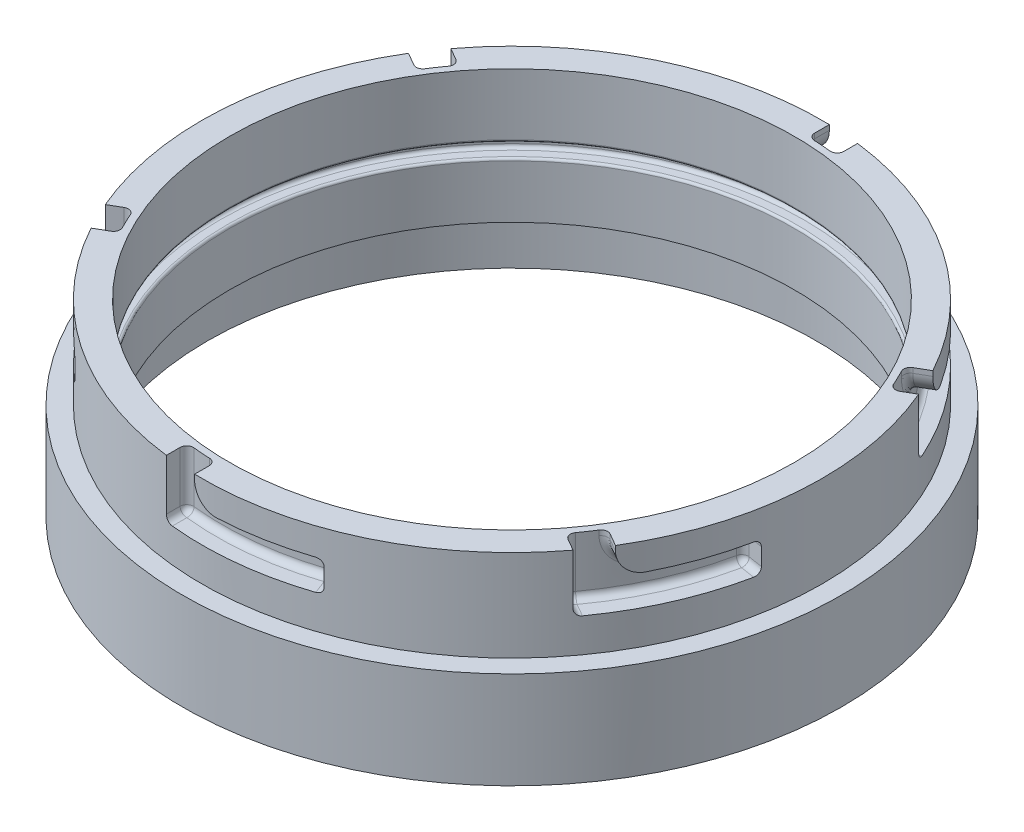
SolidWorks part; units mm, degrees
material "6061-T6 (SS)"
ref_plane "Front Plane" through (0, 0, 0) normal (0, 0, 1) x (1, 0, 0)
ref_plane "Top Plane" through (0, 0, 0) normal (0, 1, 0) x (1, 0, 0)
ref_plane "Right Plane" through (0, 0, 0) normal (1, 0, 0) x (0, 0, -1)
sketch "Sketch1" plane through (0, 0, 0) normal (0, 0, 1) x (1, 0, 0)
  line L0 (0, 60.758) -> (0, -61.3352) construction
  line L1 (71.12, 36.5125) -> (71.12, 15.5575)
  line L2 (71.12, 15.5575) -> (75.565, 15.5575)
  line L3 (75.565, 15.5575) -> (75.565, 6.0325)
  line L4 (75.565, 6.0325) -> (64.77, 6.0325)
  line L5 (64.77, 6.0325) -> (64.77, 18.7325)
  line L6 (64.77, 36.5125) -> (71.12, 36.5125)
  line L7 (64.77, 18.7325) -> (67.818, 18.7325)
  line L8 (67.818, 18.7325) -> (67.818, 21.9075)
  line L9 (67.818, 21.9075) -> (64.77, 21.9075)
  line L10 (64.77, 21.9075) -> (64.77, 36.5125)
  dimension "D1" = 6.35
  dimension "D2" = 9.525
  dimension "D3" = 30.48
  dimension "D4" = 71.12
  dimension "D5" = 75.565
  dimension "D6" = 3.048
  dimension "D7" = 12.7
  dimension "D8" = 15.875
revolve "Revolve1" add sketch "Sketch1" angle 360 about L0
sketch "Sketch2" plane through (0, 36.5125, 0) normal (0, 1, 0) x (1, 0, 0)
  line L0 (-8.6592, -70.5909) -> (-8.6592, -65.726)
  line L1 (-1.6742, -71.1003) -> (-1.6742, -66.2729)
  arc A0 (-1.6742, -71.1003) -> (-8.6592, -70.5909) centre (0, 0) cw
  circle A1 centre (0, 0) radius 71.12 construction
  arc A2 (-1.6742, -66.2729) -> (-8.6592, -65.726) centre (0, 0) cw
  dimension "D1" = 4.826
  dimension "D2" = 6.985
  dimension "D3" = 6.985
extrude "Cut-Extrude1" cut sketch "Sketch2" against normal blind 13.208
sketch "Sketch10" plane through (-1.6742, 0, 0) normal (-1, 0, 0) x (0, 0, 1)
  line L0 (66.2729, 23.3045) -> (66.2729, 30.2895)
  line L1 (66.2729, 23.3045) -> (66.2729, 36.5125) construction
  line L2 (66.2729, 30.2895) -> (71.1003, 30.2895)
  line L3 (71.1003, 23.3045) -> (71.1003, 36.5125) construction
  line L4 (71.1003, 30.2895) -> (71.1003, 23.3045)
  line L5 (71.1003, 23.3045) -> (66.2729, 23.3045)
  dimension "D1" = 6.985
ref_axis "Axis1" through (0, 6.0325, 0) along (0, 1, 0)
sketch "Sketch21" plane through (0, 23.3045, 0) normal (0, 1, 0) x (1, 0, 0)
  line L0 (-1.6742, -71.1003) -> (-1.6742, -66.2729) construction
  arc A0 (-1.6742, -73.5126) -> (73.4476, -3.5158) centre (0, 0) ccw
sketch "Sketch22" plane through (0, 23.3045, 0) normal (0, 1, 0) x (1, 0, 0)
  circle A1 centre (0, 0) radius 73.5317
sketch "Sketch23" plane through (0, 23.3045, 0) normal (0, 1, 0) x (1, 0, 0)
  arc A0 (-1.6742, -71.1003) -> (23.922, -66.9761) centre (0, 0) ccw
sweep "Cut-Sweep2" cut profiles "Sketch10" path "Sketch23"
fillet "Fillet1" radius 5.08 1 edges at (-1.6742, 30.2895, 68.6866)
fillet "Fillet7" radius 1.524 9 edges at (-1.6742, 35.941, 66.2729) (0.2383, 31.3979, 66.2936) (23.0569, 23.3045, 64.7227) (-8.6592, 23.3045, 68.1585) (23.0569, 30.2895, 64.7227) (22.1917, 26.797, 62.4694) (12.9344, 30.2895, 65.02) (6.9594, 23.3045, 65.9277) (-8.6592, 29.9085, 65.726)
pattern_circular "CirPattern1" count 6 over 360 about axis through (0, 60.758, 0) along (0, 1, 0) of "Fillet1", "Cut-Extrude1", "Cut-Sweep2", "Fillet7" reverse direction yes
fillet "Fillet2" radius 0.762 2 edges at (-67.818, 21.9075, 0) (-67.818, 18.7325, 0)
fillet "Fillet3" radius 0.508 2 edges at (-64.77, 18.7325, 0) (-64.77, 21.9075, 0)
sketch "Sketch24" plane through (0, 6.0325, 0) normal (0, -1, 0) x (1, 0, 0)
  line L0 (-2.0961, 67.1054) -> (-1.1566, 67.1033)
  line L1 (-1.6263, 67.1043) -> (-1.6325, 64.2837) construction
  line L2 (-3.1931, 64.513) -> (-0.071, 64.5062)
  spline S0 degree 3 poles (-2.0961, 67.1054) (-2.1672, 66.9295) (-2.2659, 66.6682) (-2.4002, 66.2739) (-2.4676, 66.0573) (-2.5063, 65.9255) knots 0 0 0 0 0.455486 0.670301 1 1 1 1
  spline S1 degree 3 poles (-2.5063, 65.9255) (-2.5773, 65.6449) (-2.6547, 65.2845) (-2.7636, 64.9081) (-2.7851, 64.7854) (-2.8051, 64.7157) (-2.8445, 64.6485) (-2.9065, 64.5845) (-3.0202, 64.5178) (-3.1269, 64.5162) (-3.1931, 64.513) knots 0 0 0 0 0.50758 0.647219 0.68628 0.726157 0.773713 0.821128 0.881401 1 1 1 1
  spline S2 degree 3 poles (-1.1566, 67.1033) (-1.0863, 66.9271) (-0.9887, 66.6654) (-0.8561, 66.2705) (-0.7897, 66.0536) (-0.7516, 65.9217) knots 0 0 0 0 0.455486 0.670301 1 1 1 1
  spline S3 degree 3 poles (-0.7516, 65.9217) (-0.6962, 65.7094) (-0.6454, 65.4407) (-0.5548, 65.1173) (-0.5157, 64.9486) (-0.4854, 64.8115) (-0.4614, 64.7227) (-0.4366, 64.6731) (-0.4076, 64.6316) (-0.3644, 64.5877) (-0.3091, 64.5493) (-0.2095, 64.5089) (-0.1255, 64.5109) (-0.071, 64.5062) knots 0 0 0 0 0.384807 0.478666 0.588978 0.688379 0.725395 0.749588 0.785292 0.813657 0.857185 0.902571 1 1 1 1
extrude "Cut-Extrude3" [suppressed] cut sketch "Sketch24" against normal blind 13.208
fillet "Fillet5" [suppressed] radius 0.508 tangent propagation no
fillet "Fillet6" [suppressed] radius 0.254
pattern_circular "CirPattern3" [suppressed] count 120 every 3 of bodies 114
sketch "Sketch25" plane through (0, 6.0325, 0) normal (0, -1, 0) x (1, 0, 0)
  circle A0 centre (0, 0) radius 75.565
  circle A1 centre (0, 0) radius 69.85
  dimension "D1" = 139.7
extrude "Boss-Extrude1" add sketch "Sketch25" along normal blind 12.7
fillet "Fillet8" radius 0.762 1 edges at (69.85, 6.0325, 0)
